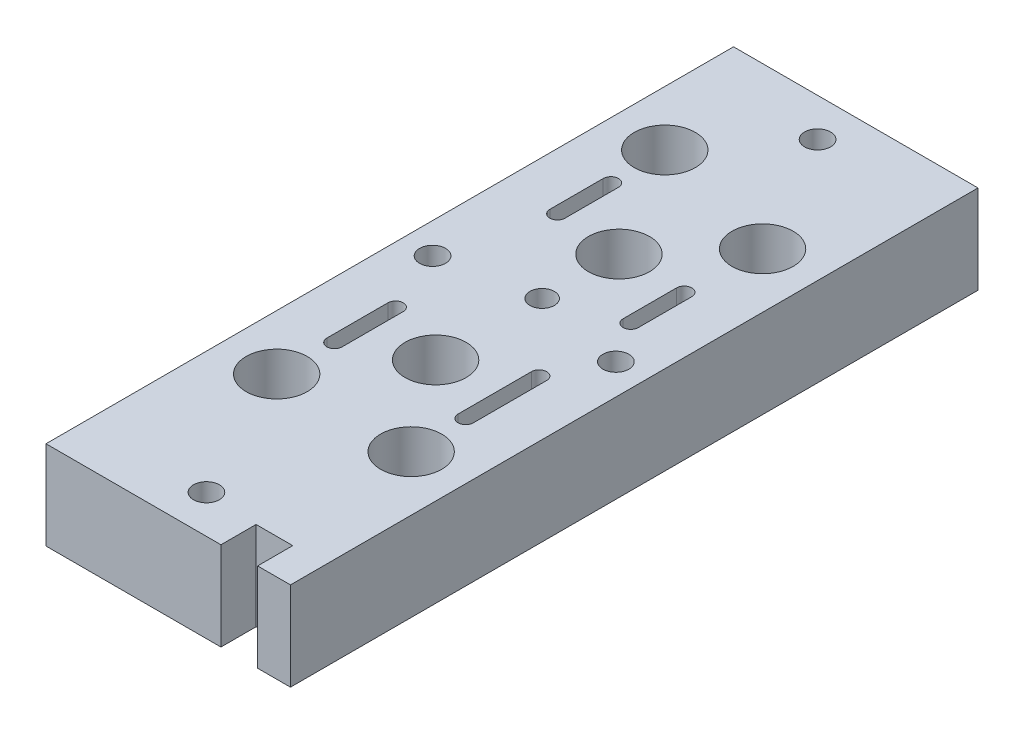
SolidWorks part; units mm, degrees
material "Plain Carbon Steel"
ref_plane "Front Plane" through (0, 0, 0) normal (0, 0, 1) x (1, 0, 0)
ref_plane "Top Plane" through (0, 0, 0) normal (0, 1, 0) x (1, 0, 0)
ref_plane "Right Plane" through (0, 0, 0) normal (1, 0, 0) x (0, 0, -1)
sketch "Sketch1" plane through (0, 0, 0) normal (0, 1, 0) x (1, 0, 0)
  line L1 (-40, -112.5) -> (40, -112.5)
  line L2 (-40, -112.5) -> (-40, 112.5)
  line L3 (-40, 112.5) -> (40, 112.5)
  line L4 (40, -112.5) -> (40, 112.5)
  line L5 (-40, -112.5) -> (40, 112.5) construction
  line L6 (-40, 112.5) -> (40, -112.5) construction
  point P0 (0, 0)
  dimension "D1" = 225
  dimension "D2" = 80
extrude "Boss-Extrude1" add sketch "Sketch1" against normal blind 29
sketch "Sketch2" plane through (0, 0, 0) normal (0, 1, 0) x (1, 0, 0)
  line L0 (-19, 36.36) -> (-19, 53.86) construction
  line L1 (-24, 53.86) -> (-24, 36.36) construction
  line L2 (-19, -36.59) -> (-19, -16.59) construction
  line L3 (-24, -16.59) -> (-24, -36.59) construction
  line L4 (24, 17.36) -> (24, 34.86) construction
  line L5 (19, 34.86) -> (19, 17.36) construction
  line L8 (24, -36.64) -> (24, -12.64) construction
  line L9 (19, -12.64) -> (19, -36.64) construction
  line L11 (-19, 36.36) -> (-19, 53.86)
  line L14 (-24, 53.86) -> (-24, 36.36)
  line L15 (-19, -36.59) -> (-19, -16.59)
  line L16 (-24, -16.59) -> (-24, -36.59)
  line L17 (24, 17.36) -> (24, 34.86)
  line L20 (19, 34.86) -> (19, 17.36)
  line L21 (24, -36.64) -> (24, -12.64)
  line L23 (19, -12.64) -> (19, -36.64)
  arc A0 (-24, 36.36) -> (-19, 36.36) centre (-21.5, 36.36) ccw construction
  arc A1 (-19, 53.86) -> (-24, 53.86) centre (-21.5, 53.86) ccw construction
  arc A2 (-24, -36.59) -> (-19, -36.59) centre (-21.5, -36.59) ccw construction
  arc A3 (-19, -16.59) -> (-24, -16.59) centre (-21.5, -16.59) ccw construction
  arc A4 (19, 17.36) -> (24, 17.36) centre (21.5, 17.36) ccw construction
  arc A5 (24, 34.86) -> (19, 34.86) centre (21.5, 34.86) ccw construction
  arc A8 (19, -36.64) -> (24, -36.64) centre (21.5, -36.64) ccw construction
  arc A9 (24, -12.64) -> (19, -12.64) centre (21.5, -12.64) ccw construction
  arc A14 (-24, 36.36) -> (-19, 36.36) centre (-21.5, 36.36) ccw
  arc A15 (-19, 53.86) -> (-24, 53.86) centre (-21.5, 53.86) ccw
  arc A16 (-24, -36.59) -> (-19, -36.59) centre (-21.5, -36.59) ccw
  arc A17 (-19, -16.59) -> (-24, -16.59) centre (-21.5, -16.59) ccw
  arc A20 (19, 17.36) -> (24, 17.36) centre (21.5, 17.36) ccw
  arc A21 (24, 34.86) -> (19, 34.86) centre (21.5, 34.86) ccw
  arc A26 (19, -36.64) -> (24, -36.64) centre (21.5, -36.64) ccw
  arc A27 (24, -12.64) -> (19, -12.64) centre (21.5, -12.64) ccw
extrude "Cut-Extrude1" cut sketch "Sketch2" against normal up to next
sketch "Sketch4" plane through (0, 0, 0) normal (0, 1, 0) x (1, 0, 0)
  circle A0 centre (-22, 72) radius 10
  circle A1 centre (22, 60) radius 10
  circle A2 centre (0, 35) radius 10
  circle A3 centre (0, -25) radius 10
  circle A4 centre (22, -55) radius 10
  circle A5 centre (-22, -55) radius 10
  dimension "D1" = 20
extrude "Cut-Extrude2" cut sketch "Sketch4" against normal blind 17
sketch "Sketch5" plane through (0, -29, 0) normal (0, -1, 0) x (1, 0, 0)
  circle A0 centre (0, 100) radius 8.5
  circle A1 centre (0, -100) radius 8.5
  dimension "D1" = 17
extrude "Cut-Extrude3" cut sketch "Sketch5" against normal blind 5
sketch "Sketch6" plane through (0, 0, 0) normal (0, 1, 0) x (1, 0, 0)
  line L0 (-40, -112.5) -> (40, -112.5) construction
  line L1 (17.25, -112.5) -> (29.25, -112.5)
  line L2 (17.25, -112.5) -> (17.25, -101)
  line L3 (17.25, -101) -> (29.25, -101)
  line L4 (29.25, -112.5) -> (29.25, -101)
  line L5 (28.25, -102.5) -> (28.25, -115) construction
  line L6 (18.25, -115) -> (18.25, -102.5) construction
  line L7 (18.75, -102) -> (27.75, -102) construction
  point P8 (28.25, -108.75)
  point P11 (18.25, -108.75)
  dimension "D1" = 1
  dimension "D2" = 1
  dimension "D3" = 1
extrude "Cut-Extrude4" cut sketch "Sketch6" against normal up to next
hole_wizard "M10 Tapped Hole1" positions "Sketch11" profile "Sketch8" tap size "M10" standard "ISO" end condition through all
sketch "Sketch11" plane through (0, 0, 0) normal (0, 1, 0) x (1, 0, 0)
  circle A0 centre (0, -100) radius 8.5 construction
  circle A1 centre (0, 100) radius 8.5 construction
  point P0 (0, -100)
  point P2 (30, 4)
  point P4 (-30, 4)
  point P6 (0, 100)
  point P12 (0, 0)
  point P15 (0, 0)
  dimension "D3" = 4
  dimension "D4" = 30
  dimension "D5" = 30
sketch "Sketch8" plane through (0, 0, 100) normal (1, 0, 0) x (0, 0, 1)
  line L0 (0, 0) -> (0, 29)
  line L1 (0, 29) -> (4.25, 29)
  line L2 (4.25, 29) -> (4.25, 0)
  line L5 (4.25, 0) -> (0, 0)
  line L11 (0, -6.35) -> (0, 107.95) construction
  dimension "Thru Tap Drill Dia." = 8.5
  dimension "Thru Tap Drill Depth" = 29
cosmetic thread "Hole Thread1" parameters "D2"=10
cosmetic thread "Hole Thread2" parameters "D2"=10
cosmetic thread "Hole Thread3" parameters "D2"=10
cosmetic thread "Hole Thread4" parameters "D2"=10
sketch "Sketch10" plane through (0, 0, 0) normal (0, 1, 0) x (1, 0, 0)
  circle A0 centre (0, 9.86) radius 5 construction
  circle A1 centre (0, 9.86) radius 5 construction
  circle A2 centre (0, 9.86) radius 4
  dimension "D1" = 8
extrude "Cut-Extrude5" cut sketch "Sketch10" against normal up to next
